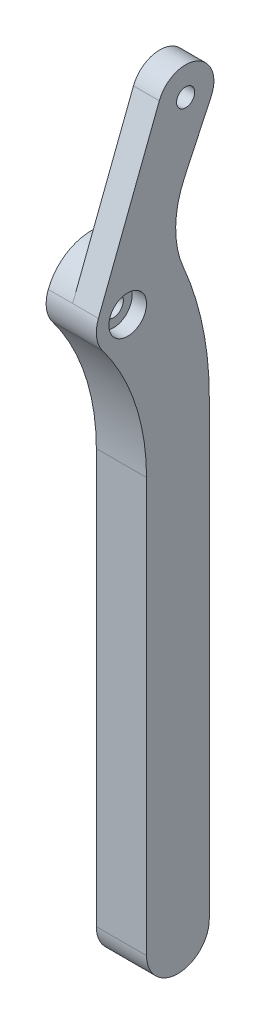
SolidWorks part; units mm, degrees
ref_plane "Front Plane" through (0, 0, 0) normal (0, 0, 1) x (1, 0, 0)
ref_plane "Top Plane" through (0, 0, 0) normal (0, 1, 0) x (1, 0, 0)
ref_plane "Right Plane" through (0, 0, 0) normal (1, 0, 0) x (0, 0, -1)
sketch "Sketch1" plane through (0, 0, 0) normal (1, 0, 0) x (0, 0, -1)
  line L0 (13, -90) -> (13, -17.7993)
  line L1 (5.0352, 26.9888) -> (-4.666, 1.7968)
  line L2 (3, -90) -> (3, -24)
  line L3 (0, 0) -> (9.2345, 25.3717) construction
  line L4 (0, 0) -> (0, 25.3717) construction
  line L5 (0, 25.3717) -> (9.2345, 25.3717) construction
  line L6 (9.0631, 14.4072) -> (13.3088, 23.4611)
  circle A0 centre (0, 0) radius 5
  circle A1 centre (9.2345, 25.3717) radius 4.5
  circle A2 centre (8, -90) radius 5
  arc A3 (3, -24) -> (-4, -3) centre (-32, -24) ccw
  arc A4 (13, -17.7993) -> (8.88, 2.076) centre (-37, -17.7993) ccw
  arc A5 (8.88, 2.076) -> (9.0631, 14.4072) centre (22.644, 8.0386) cw
  circle A6 centre (9.2345, 25.3717) radius 1.45
  circle A7 centre (0, 0) radius 1.6
  arc A8 (8.88, 2.076) -> (-4.666, 1.7968) centre (2.1641, -0.8334) ccw
  point P24 (-3.6674, 4.2396)
  point P26 (-4.666, 2.434)
  dimension "D2" = 9
  dimension "D3" = 10
  dimension "D4" = 10
  dimension "D7" = 15
  dimension "D9" = 50
  dimension "D10" = 35
  dimension "D12" = 2.9
  dimension "D13" = 3.2
  dimension "D1" = 20
  dimension "D5" = 3
  dimension "D6" = 90
  dimension "D8" = 27
  dimension "D11" = 10
extrude "Boss-Extrude1" add sketch "Sketch1" along normal mid plane 8 contours A1 A6 | A5 L6 A1 L1 A0 | A0 A7 | L0 A4 A0 A3 L2 A2 | A2 region at (0, -41.085, -7.5555) region at (0, -90, -8) region at (0, 13.7046, -4.4718) region at (0, 4.7767, -0.888) region at (0, 21.3494, -7.5195)
sketch "Sketch2" plane through (4, 0, 0) normal (1, 0, 0) x (0, 0, -1)
  circle A0 centre (0, 0) radius 3
  dimension "D1" = 6
extrude "Cut-Extrude1" cut sketch "Sketch2" against normal blind 2.3
mirror "Mirror1" about plane through (0, 0, 0) normal (1, 0, 0) of "Cut-Extrude1"
extrude "Cut-Extrude2" cut sketch "Sketch1<5>" against normal through all from offset 0.12 contours A8 A5 L6 A1 L1 | A1 A6 region at (0, 13.7046, -4.4718) region at (0, 21.3494, -7.5195) offset against normal yes
sketch "Sketch1<5>" plane through (0, 0, 0) normal (1, 0, 0) x (0, 0, -1) same geometry as "Sketch1"
